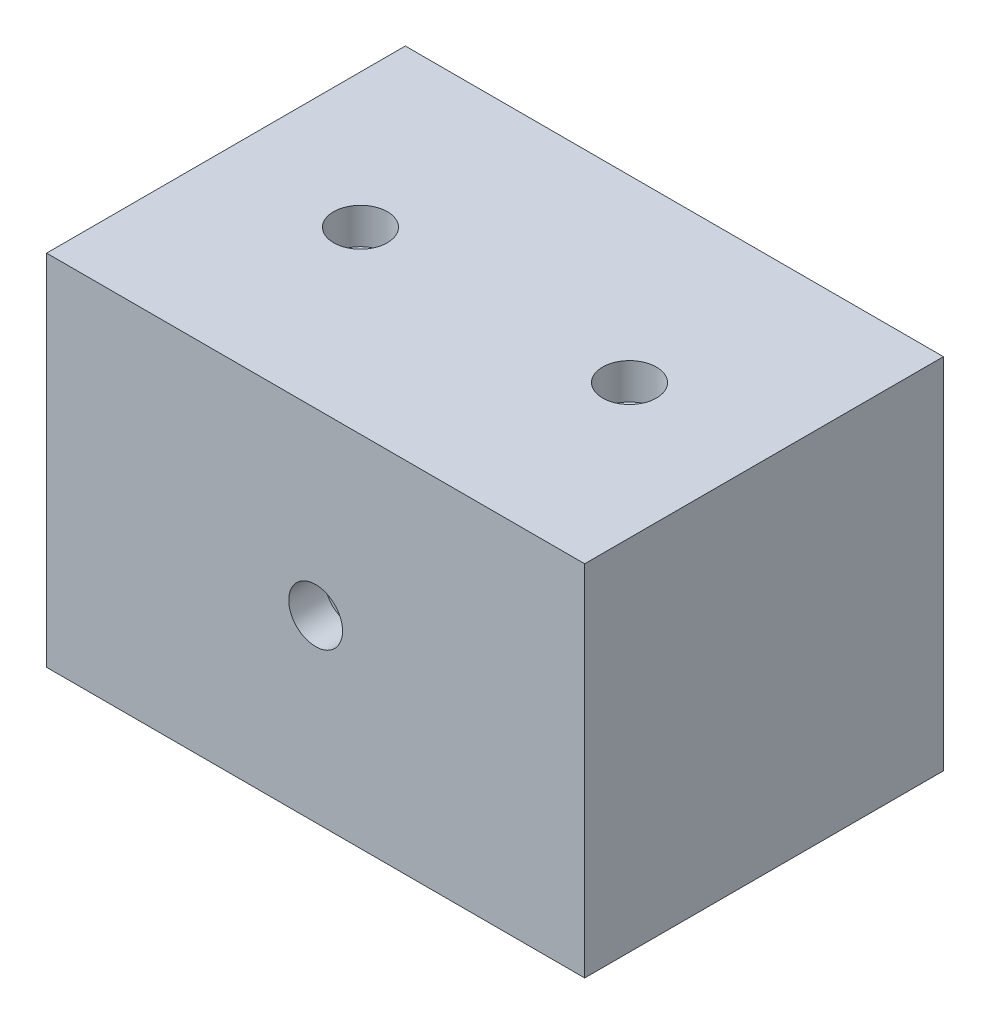
SolidWorks part; units mm, degrees
ref_plane "Front Plane" through (0, 0, 0) normal (0, 0, 1) x (1, 0, 0)
ref_plane "Top Plane" through (0, 0, 0) normal (0, 1, 0) x (1, 0, 0)
ref_plane "Right Plane" through (0, 0, 0) normal (1, 0, 0) x (0, 0, -1)
sketch "Sketch1" plane through (0, 0, 0) normal (0, 0, 1) x (1, 0, 0)
  line L1 (0, 0) -> (30, 0)
  line L2 (0, 0) -> (0, 20)
  line L3 (0, 20) -> (30, 20)
  line L4 (30, 0) -> (30, 20)
  dimension "D1" = 30
  dimension "D2" = 20
extrude "Boss-Extrude1" add sketch "Sketch1" along normal blind 20
sketch "Sketch2" plane through (0, 0, 20) normal (0, 0, 1) x (1, 0, 0)
  line L0 (15, 20) -> (15, 0) construction
  line L1 (30, 20) -> (0, 20) construction
  line L2 (0, 0) -> (30, 0) construction
  circle A0 centre (15, 10) radius 1.5
  dimension "D1" = 3
extrude "Cut-Extrude1" cut sketch "Sketch2" against normal blind 2
sketch "Sketch3" plane through (0, 20, 0) normal (0, 1, 0) x (1, 0, 0)
  line L1 (0, -20) -> (0, 0) construction
  line L2 (30, -20) -> (30, 0) construction
  line L3 (30, -10) -> (15, -10) construction
  line L4 (15, -10) -> (0, -10) construction
  line L5 (0, -10) -> (15, -10) construction
  line L6 (15, -10) -> (30, -10) construction
  circle A0 centre (7.5, -10) radius 1.5
  circle A1 centre (22.5, -10) radius 1.5
  dimension "D1" = 3
extrude "Cut-Extrude2" cut sketch "Sketch3" against normal blind 2
